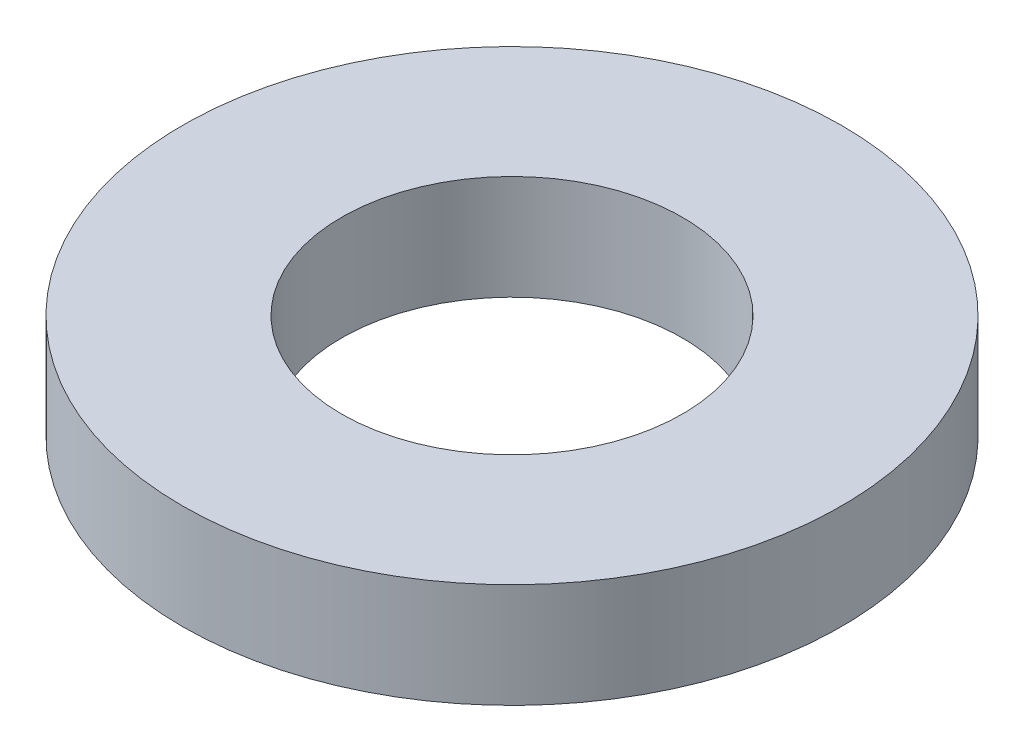
SolidWorks part; units mm, degrees
ref_plane "Front Plane" through (0, 0, 0) normal (0, 0, 1) x (1, 0, 0)
ref_plane "Top Plane" through (0, 0, 0) normal (0, 1, 0) x (1, 0, 0)
ref_plane "Right Plane" through (0, 0, 0) normal (1, 0, 0) x (0, 0, -1)
sketch "Sketch1" plane through (0, 0, 0) normal (0, 1, 0) x (1, 0, 0)
  circle A0 centre (0, 0) radius 72.5
  dimension "FLANGE_OD" = 145
extrude "Boss-Extrude1" add sketch "Sketch1" along normal blind 23
sketch "Sketch2" plane through (0, 0, 0) normal (0, 1, 0) x (1, 0, 0)
  circle A0 centre (0, 0) radius 37.5
  dimension "BORE_D" = 75
extrude "Cut-Extrude1" cut sketch "Sketch2" along normal through all
sketch "Sketch3" plane through (0, 23, 0) normal (0, 1, 0) x (1, 0, 0)
  circle A0 centre (0, 0) radius 30.9388 construction
  circle A1 centre (-30.9388, 0) radius 2.9548
  dimension "BOLT_D" = 5.9096
  dimension "BOLT_PCD" = 61.8777
extrude "Cut-Extrude2" cut sketch "Sketch3" against normal blind 16.7419 rebuild error yes
pattern_circular "CirPattern1" count 8 over 360 rebuild error yes
